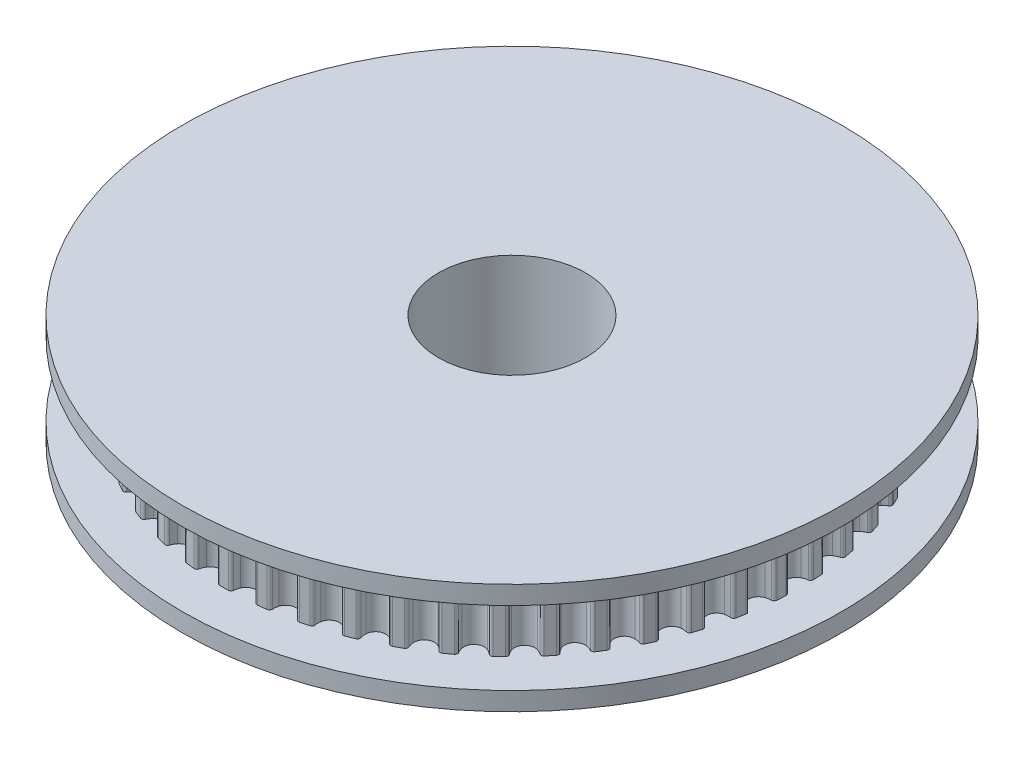
SolidWorks part; units mm, degrees
ref_plane "Front Plane" through (0, 0, 0) normal (0, 0, 1) x (1, 0, 0)
ref_plane "Top Plane" through (0, 0, 0) normal (0, 1, 0) x (1, 0, 0)
ref_plane "Right Plane" through (0, 0, 0) normal (1, 0, 0) x (0, 0, -1)
sketch "Sketch1" plane through (0, 0, 0) normal (0, 1, 0) x (1, 0, 0)
  circle A0 centre (0, 0) radius 15.9155
  dimension "D1" = 31.831
extrude "Boss-Extrude1" add sketch "Sketch1" along normal mid plane 4
sketch "Sketch2" plane through (0, 0, 0) normal (0, 1, 0) x (1, 0, 0)
  line L0 (0, 0) -> (0, 15.6615) construction
  line L1 (0, 0) -> (0.9711, 15.436) construction
  line L2 (0, 15.6615) -> (0, 15.9155)
  line L3 (0.9711, 15.436) -> (0.9993, 15.8841) construction
  line L4 (0.9993, 15.8841) -> (1.3982, 15.854) construction
  line L5 (1.3982, 15.854) -> (1.3799, 15.6119) construction
  line L6 (1.9629, 15.538) -> (1.9947, 15.79)
  arc A1 (0, 15.6615) -> (0.2367, 15.6597) centre (0, 0) cw
  arc A2 (0.2367, 15.6597) -> (0.3839, 15.523) centre (0.2345, 15.5097) cw
  arc A3 (0.3839, 15.523) -> (0.4613, 15.2166) centre (1.3799, 15.6119) ccw
  arc A4 (0.4613, 15.2166) -> (1.4494, 15.1545) centre (0.9711, 15.436) ccw
  circle A5 centre (0, 0) radius 15.9155 construction
  arc A6 (0, 15.9155) -> (1.9947, 15.79) centre (0, 0) cw
  arc A7 (1.5647, 15.4488) -> (1.4494, 15.1545) centre (0.5876, 15.6617) cw
  arc A8 (1.7278, 15.5659) -> (1.5647, 15.4488) centre (1.7113, 15.4168) ccw
  arc A9 (1.9629, 15.538) -> (1.7278, 15.5659) centre (0, 0) ccw
  point P23 (1.3685, 6.2174)
  point P24 (0, 0)
  point P25 (1.3438, 6.0134)
  dimension "D2" = 0.15
  dimension "D3" = 1
  dimension "D4" = 0.555
  dimension "D1" = 3.6
  dimension "D5" = 0.254
  dimension "D6" = 0.4
  dimension "D7" = 1.004
extrude "Cut-Extrude1" cut sketch "Sketch2" against normal through all both and the other way through all
pattern_circular "CirPattern1" count 50 over 360 about axis through (0, 2, 0) along (0, -1, 0) of "Cut-Extrude1"
sketch "Sketch3" plane through (0, 0, 0) normal (0, 1, 0) x (1, 0, 0)
  circle A0 centre (0, 0) radius 17.9155
  dimension "D1" = 35.831
extrude "Boss-Extrude2" add sketch "Sketch3" along normal blind 1 from surface starting at face at (0, 2, 0)
extrude "Boss-Extrude3" add sketch "Sketch3<2>" against normal blind 1 from surface starting at face at (0, -2, 0)
sketch "Sketch3<2>" plane through (0, 0, 0) normal (0, 1, 0) x (1, 0, 0) same geometry as "Sketch3"
sketch "Sketch4" plane through (0, 0, 0) normal (0, 1, 0) x (1, 0, 0)
  circle A0 centre (0, 0) radius 4
  dimension "D1" = 8
extrude "Cut-Extrude2" cut sketch "Sketch4" against normal through all both and the other way through all
equation "\"n\"= 50"
equation "\"p\"= 2mm"
equation "\"pd\"= ( \"n\" * \"p\" ) / pi"
equation "\"D1@Sketch1\"=\"pd\""
equation "\"D1@Sketch2\"=180/\"n\""
equation "\"D1@CirPattern1\"=\"n\""
equation "\"D1@Sketch3\"=\"pd\"+4mm"
